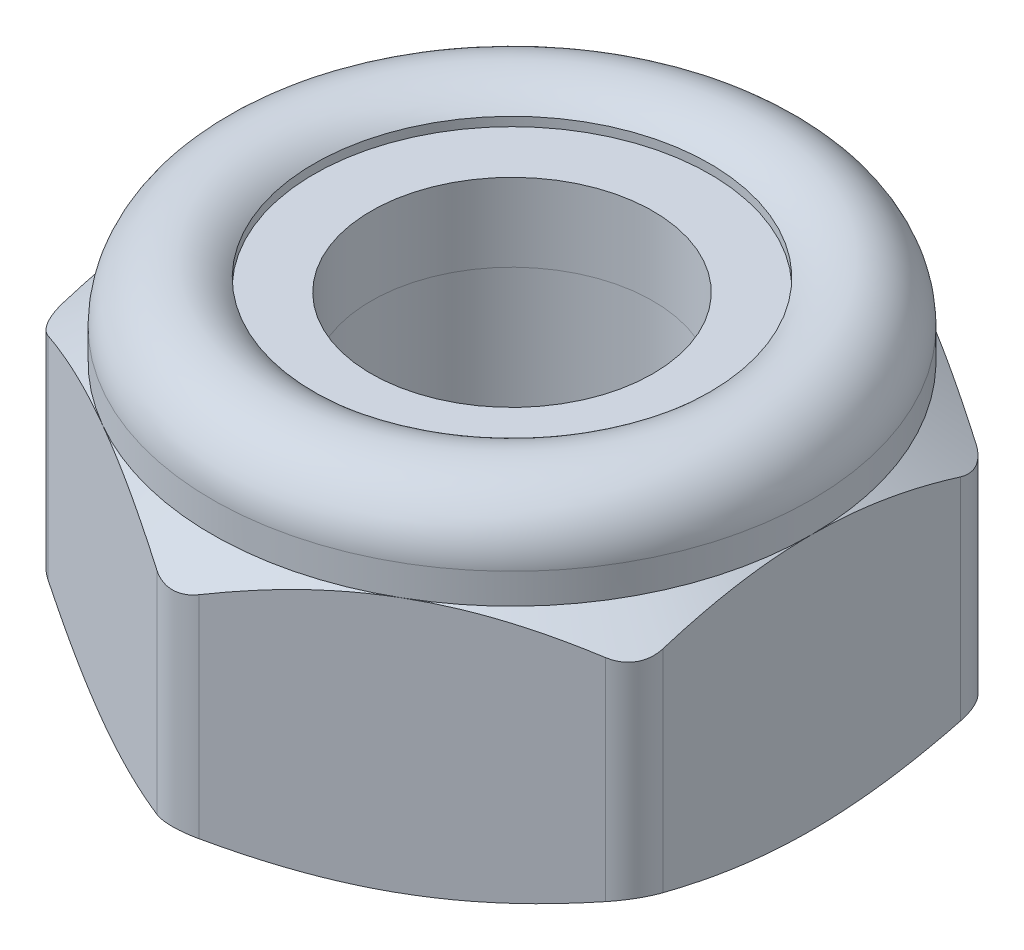
SolidWorks part; units mm, degrees
ref_plane "Front Plane" through (0, 0, 0) normal (0, 0, 1) x (1, 0, 0)
ref_plane "Top Plane" through (0, 0, 0) normal (0, 1, 0) x (1, 0, 0)
ref_plane "Right Plane" through (0, 0, 0) normal (1, 0, 0) x (0, 0, -1)
sketch "Sketch1" plane through (0, 0, 0) normal (0, 0, 1) x (1, 0, 0)
  line L0 (0, -3) -> (0, 3) construction
  line L1 (5, 0) -> (-5, 0) construction
  line L2 (3, -3) -> (-3, -3) construction
  line L3 (3, -3) -> (3, -2) construction
  point P4 (0, 0)
  point P8 (0, 0)
  point P11 (0, -3)
  dimension "Height" = 6
  dimension "Width" = 10
  dimension "Thread Size" = 6
  dimension "Thread Pitch" = 1
sketch "Sketch2" plane through (0, 0, 0) normal (0, 1, 0) x (1, 0, 0)
  line L0 (-3, 0.4375) -> (-3, -0.4375) construction
  line L1 (0, 5.7735) -> (-5, 2.8868)
  line L2 (-5, 2.8868) -> (-5, -2.8868)
  line L3 (-5, -2.8868) -> (0, -5.7735)
  line L4 (0, -5.7735) -> (5, -2.8868)
  line L5 (5, -2.8868) -> (5, 2.8868)
  line L6 (5, 2.8868) -> (0, 5.7735)
  line L7 (-3, -0.4375) -> (-2.3505, -0.0625) construction
  line L8 (-2.3505, -0.0625) -> (-2.3505, 0.0625) construction
  line L9 (-2.3505, 0.0625) -> (-3, 0.4375) construction
  line L10 (-2.3505, 0) -> (-3, 0) construction
  line L11 (-2.6752, 0.25) -> (-2.6752, -0.25) construction
  line L12 (3, 0) -> (-3, 0) construction
  line L13 (5, 0) -> (-5, 0) construction
  circle A0 centre (0, 0) radius 5 construction
  circle A1 centre (0, 0) radius 2.3505
  point P19 (0, -2.3505)
  dimension "D1" = 0.125
  dimension "D2" = 0.5
  dimension "D3" = 60
extrude "Boss-Extrude1" add sketch "Sketch2" along normal up to vertex (3 mm away) and the other way up to vertex (3 mm away) up to point (0, 3, 0) other way up to point (0, -3, 0)
fillet "Fillet1" radius 0.7 6 edges at (-5, 0, -2.8868) (0, 0, -5.7735) (-5, 0, 2.8868) (5, 0, -2.8868) (5, 0, 2.8868) (0, 0, 5.7735)
sketch "Sketch3" plane through (0, 0, 0) normal (1, 0, 0) x (0, 0, -1)
  line L0 (5.7735, 1.5) -> (5.7735, 4)
  line L1 (3.3, 1.2) -> (5, 1.2) construction
  line L2 (4.6, -3) -> (5.7735, -2.3225)
  line L3 (3.0888, -3) -> (5.5714, -3) construction
  line L4 (5.7735, 3) -> (5.7735, -3) construction
  line L5 (5.7735, -2.3225) -> (5.7735, -3)
  line L6 (5.7735, -3) -> (4.6, -3)
  line L7 (5, 1.5) -> (5.7735, 0.9584)
  line L8 (5.7735, 0.9584) -> (5.7735, 1.5)
  line L9 (5, 1.2) -> (5, 1.5) construction
  line L10 (3.0888, -3) -> (5.5714, -3) construction
  line L11 (5, 1.5) -> (5, 2.0042)
  line L12 (3.0888, 3) -> (5.5714, 3) construction
  line L13 (2.3505, 1.2) -> (3.3, 1.2)
  line L14 (3.3, 1.2) -> (3.3, 2.7083)
  line L16 (3.3, 2.7083) -> (4.0042, 2.0042) construction
  line L17 (4.0042, 2.0042) -> (4.0042, 3) construction
  line L18 (2.3505, 1.2) -> (2.3505, 4)
  line L19 (2.3505, 4) -> (5.7735, 4)
  line L21 (2.3505, -3) -> (2.3505, -2.4)
  line L22 (-2.4826, -3) -> (2.4826, -3) construction
  line L24 (2.9505, -3) -> (2.3505, -3)
  line L25 (2.3505, -2.4) -> (2.9505, -3)
  line L26 (0, 3) -> (0, -3) construction
  line L27 (-2.4826, 3) -> (2.4826, 3) construction
  line L28 (-2.4826, -3) -> (2.4826, -3) construction
  arc A0 (5, 2.0042) -> (3.3, 2.7083) centre (4.0042, 2.0042) ccw
  point P0 (5, 1.5)
  point P1 (5, 0)
  point P14 (2.3505, 0)
  point P36 (5, -3)
  dimension "D1" = 4.5
  dimension "D2" = 30
  dimension "D3" = 45
  dimension "D4" = 1
  dimension "D5" = 0.6
  dimension "D6" = 4.2
  dimension "D7" = 0.4
  dimension "D8" = 35
  dimension "D9" = 6.6
revolve "Cut-Revolve2" cut sketch "Sketch3" angle 360 about L0
sketch "Sketch12" plane through (0, 0, 0) normal (1, 0, 0) x (0, 0, -1)
  line L0 (4.0042, 2.0042) -> (4.0042, 3) construction
  line L1 (3.3, 1.2) -> (4.0042, 1.2)
  line L2 (3.3, 1.2) -> (3.3, 2.5583)
  line L3 (3.3, 2.5583) -> (4.0042, 2.5583)
  line L4 (4.0042, 1.2) -> (4.0042, 2.5583)
  dimension "D1" = 0.15
revolve "Cut-Revolve3" cut sketch "Sketch12" angle 360 about L26
sketch "Sketch4" plane through (0, 0, 0) normal (1, 0, 0) x (0, 0, -1)
  line L1 (2.3505, 1.2) -> (4.0042, 1.2)
  line L2 (2.3505, 1.2) -> (2.3505, 2.4983)
  line L3 (2.3505, 2.4983) -> (4.0042, 2.4983)
  line L4 (4.0042, 1.2) -> (4.0042, 2.4983)
  line L5 (3.3, 2.7083) -> (-3.3, 2.7083) construction
  line L7 (4.0042, 2.0042) -> (4.0042, 3) construction
  dimension "D1" = 0.21
revolve "Revolve1" add sketch "Sketch4" angle 360 about L0
sketch "Sketch5" plane through (0, 0, 0) normal (0, 1, 0) x (1, 0, 0)
  circle A0 centre (0, 0) radius 2.3505 construction
  point P0 (0, -2.3505)
sketch "Sketch6" [suppressed] plane through (0, 0, 0) normal (1, 0, 0) x (0, 0, -1)
  line L0 (2.9505, 1.2) -> (2.9505, -3)
  line L3 (2.9505, -3) -> (0, -3)
  line L4 (0, -3) -> (0, 1.2)
  line L5 (0, -3) -> (0, 3) construction
  line L6 (0, 1.2) -> (2.9505, 1.2)
  line L7 (-2.9505, -3) -> (2.9505, -3) construction
  line L9 (2.3505, 1.2) -> (3.3, 1.2) construction
revolve "Revolve2" [suppressed] add sketch "Sketch6" angle 360 about L4
sketch "Sketch7" [suppressed] plane through (0, -3, 0) normal (0, -1, 0) x (1, 0, 0)
  circle A2 centre (0, 0) radius 2.9505
  circle A3 centre (0, 0) radius 2.9505
  dimension "D1" = 0
curve "Helix/Spiral1" [suppressed] pitch 1 height 6 turns 6
sketch "Sketch8" [suppressed] plane through (0, 0, 0) normal (0, 0, 1) x (1, 0, 0)
  line L0 (3.0587, -2.9375) -> (2.1927, -3.4375) construction
  line L1 (2.1927, -3.4375) -> (3.0587, -3.9375) construction
  line L2 (3.0587, -3.9375) -> (3.0587, -2.9375) construction
  line L3 (2.301, -3.375) -> (2.301, -3.5)
  line L4 (2.9505, -3) -> (2.9505, -3.875) construction
  line L5 (2.9505, -3.4375) -> (3.0587, -3.4375) construction
  line L6 (2.1927, -3.4375) -> (2.301, -3.4375) construction
  line L7 (3.0046, -3.4375) -> (3.0046, -3.9062) construction
  line L8 (2.301, -3.375) -> (3.0587, -2.9375)
  line L9 (3.0587, -2.9375) -> (3.0046, -3.9062)
  line L10 (2.301, -3.5) -> (3.0046, -3.9062)
  dimension "D1" = 1
  dimension "D2" = 0.125
sweep "Cut-Sweep1" [suppressed] cut profiles "Sketch8" path "Helix/Spiral1"
sketch "Sketch9" [suppressed] plane through (0, 0, 0) normal (0, 0, 1) x (1, 0, 0)
  line L5 (0, 0) -> (0, -3)
  line L6 (0, -3) -> (3, -3)
  line L7 (3, -3) -> (0, 0)
revolve "Revolve3" [suppressed] add sketch "Sketch9" angle 360 about L5
sketch "Sketch10" [suppressed] plane through (0, -3, 0) normal (0, -1, 0) x (1, 0, 0)
  circle A0 centre (0, 0) radius 2.9505 construction
  circle A1 centre (0, 0) radius 2.9505
extrude "Boss-Extrude2" [suppressed] add sketch "Sketch10" against normal up to surface (4.2 mm away)
combine bodies "Combine1" [suppressed] operation type subtract main body 110 bodies to subtract 109
equation "\"D1@Sketch3\"=\"Height@Sketch1\" *.75"
equation "\"D5@Sketch3\"=\"Thread Size@Sketch1\"*.1"
equation "\"D4@Helix/Spiral1\"=\"Thread Pitch@sketch1\""
equation "\"D3@Helix/Spiral1\"=\"Height@sketch1\""
equation "\"D1@Sketch8\"=\"Thread Pitch@sketch1\""
equation "\"D2@Sketch8\"=\"Thread Pitch@sketch1\"/8"
equation "\"D1@Sketch2\"=\"Thread Pitch@sketch1\"/8"
equation "\"D2@Sketch2\"=\"Thread Pitch@sketch1\"/2"
equation "\"D1@Sketch4\"=\"Height@Sketch1\" * .035"
equation "\"D1@Fillet1\"=\"Width@Sketch1\" * .07"
equation "\"D6@Sketch3\"=\"Height@Sketch1\" *.7"
equation "\"D7@Sketch3\"=\"Width@Sketch1\"*.04"
equation "\"D9@Sketch3\"=\"Thread Size@Sketch1\"*1.1"
equation "\"D1@Sketch12\"=\"Height@Sketch1\" * .025"
